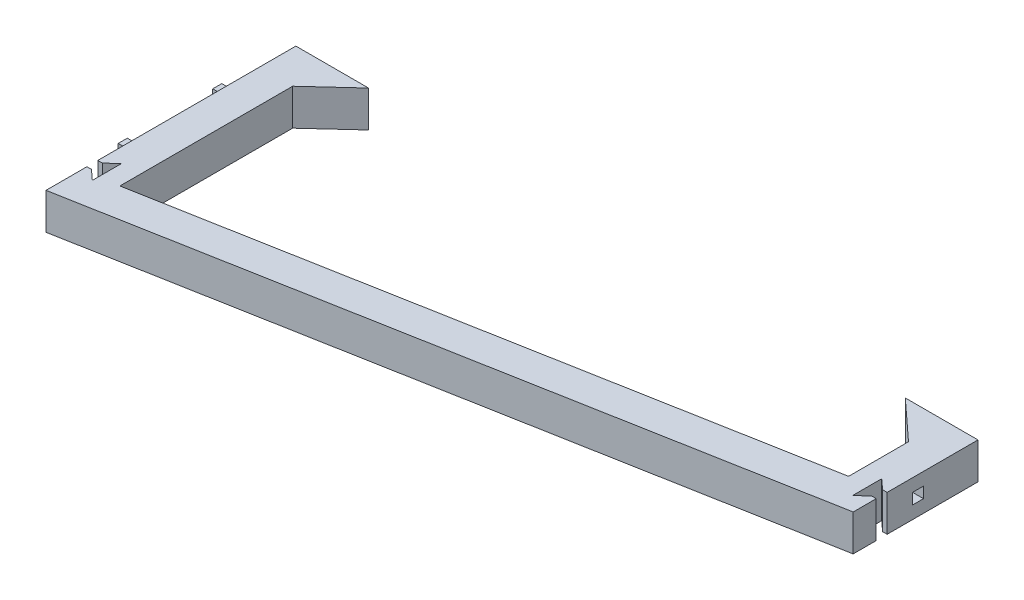
SolidWorks part; units mm, degrees
ref_plane "Přední rovina" through (0, 0, 0) normal (0, 0, 1) x (1, 0, 0)
ref_plane "Horní rovina" through (0, 0, 0) normal (0, 1, 0) x (1, 0, 0)
ref_plane "Pravá rovina" through (0, 0, 0) normal (1, 0, 0) x (0, 0, -1)
sketch "Skica1" plane through (0, 0, 0) normal (0, 1, 0) x (1, 0, 0)
  line L0 (0, 0) -> (0, -55)
  line L1 (0, -55) -> (150.15, -27.4721)
  line L2 (150.15, -27.4721) -> (150.15, 0)
  line L3 (150.15, 0) -> (142.85, 0)
  line L4 (142.85, 0) -> (142.85, -21.1855)
  line L5 (142.85, -21.1855) -> (7.3, -46.0366)
  line L6 (7.3, -46.0366) -> (7.3, 0)
  line L7 (7.3, 0) -> (0, 0)
  dimension "D1" = 7.3
  dimension "D2" = 7.3
  dimension "D3" = 55
  dimension "D4" = 7.5
  dimension "D5" = 150.15
  dimension "D6" = 27.4721
extrude "Přidat vysunutím1" add sketch "Skica1" along normal blind 8
sketch "Skica2" plane through (0, 8, 0) normal (0, 1, 0) x (1, 0, 0)
  line L5 (0, -43.6) -> (1, -43.6)
  line L6 (0, 0) -> (0, -55) construction
  line L7 (1, -43.6) -> (3.2, -41.6)
  line L8 (3.2, -41.6) -> (3.2, -48)
  line L9 (3.2, -48) -> (1, -46)
  line L10 (1, -46) -> (0, -46)
  line L11 (0, -46) -> (0, -43.6)
  dimension "D1" = 6.4
  dimension "D2" = 2.4
  dimension "D3" = 1
  dimension "D4" = 1
  dimension "D5" = 2
  dimension "D6" = 3.2
  dimension "D7" = 7
extrude "Odebrat vysunutím1" cut sketch "Skica2" against normal through all
sketch "Skica3" plane through (0, 0, 0) normal (-1, 0, 0) x (0, 0, 1)
  line L0 (0, 8) -> (0, 0) construction
  line L1 (12.3, 5) -> (14.3, 5)
  line L2 (12.3, 5) -> (12.3, 3)
  line L3 (12.3, 3) -> (14.3, 3)
  line L4 (14.3, 5) -> (14.3, 3)
  line L5 (33.1, 5) -> (35.1, 5)
  line L6 (33.1, 5) -> (33.1, 3)
  line L7 (33.1, 3) -> (35.1, 3)
  line L8 (35.1, 5) -> (35.1, 3)
  line L17 (0, 8) -> (43.6, 8) construction
  point P16 (12.3, 4)
  dimension "D1" = 12.3
  dimension "D2" = 2
  dimension "D3" = 2
  dimension "D4" = 3
  dimension "D5" = 2
  dimension "D6" = 2
  dimension "D7" = 3
  dimension "D8" = 18.8
extrude "Přidat vysunutím2" add sketch "Skica3" along normal blind 4
sketch "Skica5" plane through (0, 8, 0) normal (0, 1, 0) x (1, 0, 0)
  line L0 (0, 0) -> (0, -43.6) construction
  line L1 (0, 0) -> (16, 0)
  line L2 (0, 0) -> (0, -8)
  line L3 (0, -8) -> (16, -8)
  line L4 (16, 0) -> (16, -8)
  line L5 (150.15, -27.4721) -> (150.15, 0) construction
  line L6 (150.15, 0) -> (134.15, 0)
  line L7 (150.15, 0) -> (150.15, -8)
  line L8 (150.15, -8) -> (134.15, -8)
  line L9 (134.15, 0) -> (134.15, -8)
  line L12 (7.3, 0) -> (0, 0) construction
  line L13 (150.15, 0) -> (142.85, 0) construction
  dimension "D1" = 8
  dimension "D2" = 8
  dimension "D3" = 16
  dimension "D4" = 16
extrude "Přidat vysunutím3" add sketch "Skica5" against normal blind 8
sketch "Skica7" plane through (0, 0, 0) normal (0, -1, 0) x (1, 0, 0)
  line L0 (7.3, 8) -> (16, 0)
  line L1 (16, 0) -> (16, 8)
  line L2 (16, 8) -> (7.3, 8)
  line L3 (134.15, 0) -> (134.15, 8)
  line L4 (134.15, 8) -> (142.85, 8)
  line L5 (142.85, 8) -> (134.15, 0)
extrude "Odebrat vysunutím4" cut sketch "Skica7" against normal through all
sketch "Skica4" plane through (150.15, 0, 0) normal (1, 0, 0) x (0, 0, -1)
  line L0 (-27.4721, 8) -> (0, 8) construction
  line L5 (-14.4, 5.2) -> (-12, 5.2)
  line L6 (-14.4, 5.2) -> (-14.4, 2.8)
  line L7 (-14.4, 2.8) -> (-12, 2.8)
  line L8 (-12, 5.2) -> (-12, 2.8)
  line L13 (0, 8) -> (0, 0) construction
  dimension "D1" = 2.4
  dimension "D2" = 2.4
  dimension "D3" = 2.8
  dimension "D4" = 12
extrude "Odebrat vysunutím2" cut sketch "Skica4" against normal blind 4.4
sketch "Skica8" plane through (0, 8, 0) normal (0, 1, 0) x (1, 0, 0)
  line L6 (150.15, -20) -> (149.15, -20)
  line L7 (150.15, -27.4721) -> (150.15, 0) construction
  line L8 (149.15, -20) -> (146.95, -18)
  line L9 (146.95, -18) -> (146.95, -24.4)
  line L10 (146.95, -24.4) -> (149.15, -22.4)
  line L11 (150.15, -22.4) -> (150.15, -20)
  line L12 (149.15, -22.4) -> (150.15, -22.4)
  line L13 (150.15, 0) -> (134.15, 0) construction
  point P10 (142.15, 0)
  dimension "D1" = 6.4
  dimension "D2" = 1
  dimension "D3" = 2.4
  dimension "D4" = 2
  dimension "D5" = 3.2
  dimension "D6" = 18
  dimension "D7" = 1
extrude "Odebrat vysunutím5" cut sketch "Skica8" against normal through all
sketch "Skica11" plane through (0, 0, 0) normal (0, 0, -1) x (-1, 0, 0)
  line L0 (-150.15, 0) -> (-134.15, 0) construction
  line L2 (-150.15, 8) -> (-150.15, 0) construction
  line L3 (-16, 8) -> (0, 8) construction
  line L4 (0, 8) -> (0, 0) construction
  circle A0 centre (-146.5, 4) radius 2.2
  circle A1 centre (-3.65, 4) radius 2.2
  dimension "D1" = 4.4
  dimension "D4" = 4.4
  dimension "D2" = 4
  dimension "D3" = 3.65
  dimension "D5" = 4
  dimension "D6" = 3.65
extrude "Odebrat vysunutím7" cut sketch "Skica11" against normal blind 9.4
